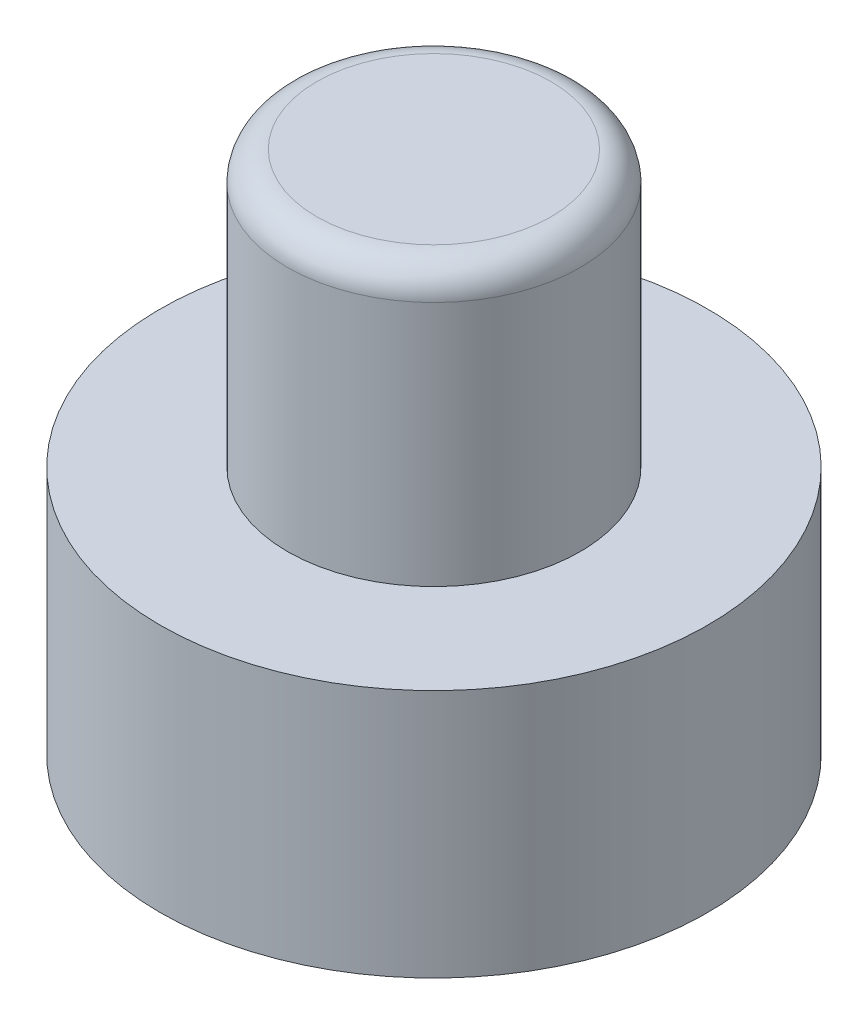
SolidWorks part; units mm, degrees
ref_plane "Front Plane" through (0, 0, 0) normal (0, 0, 1) x (1, 0, 0)
ref_plane "Top Plane" through (0, 0, 0) normal (0, 1, 0) x (1, 0, 0)
ref_plane "Right Plane" through (0, 0, 0) normal (1, 0, 0) x (0, 0, -1)
sketch "Sketch1" plane through (0, 0, 0) normal (0, 1, 0) x (1, 0, 0)
  circle A0 centre (0, 0) radius 4.675
  dimension "D1" = 9.35
extrude "Boss-Extrude1" add sketch "Sketch1" along normal blind 4.25
sketch "Sketch2" plane through (0, 4.25, 0) normal (0, 1, 0) x (1, 0, 0)
  circle A0 centre (0, 0) radius 2.5
  dimension "D1" = 5
extrude "Boss-Extrude2" add sketch "Sketch2" along normal blind 4.7
fillet "Fillet1" radius 0.5 1 edges at (0, 8.95, 2.5)
